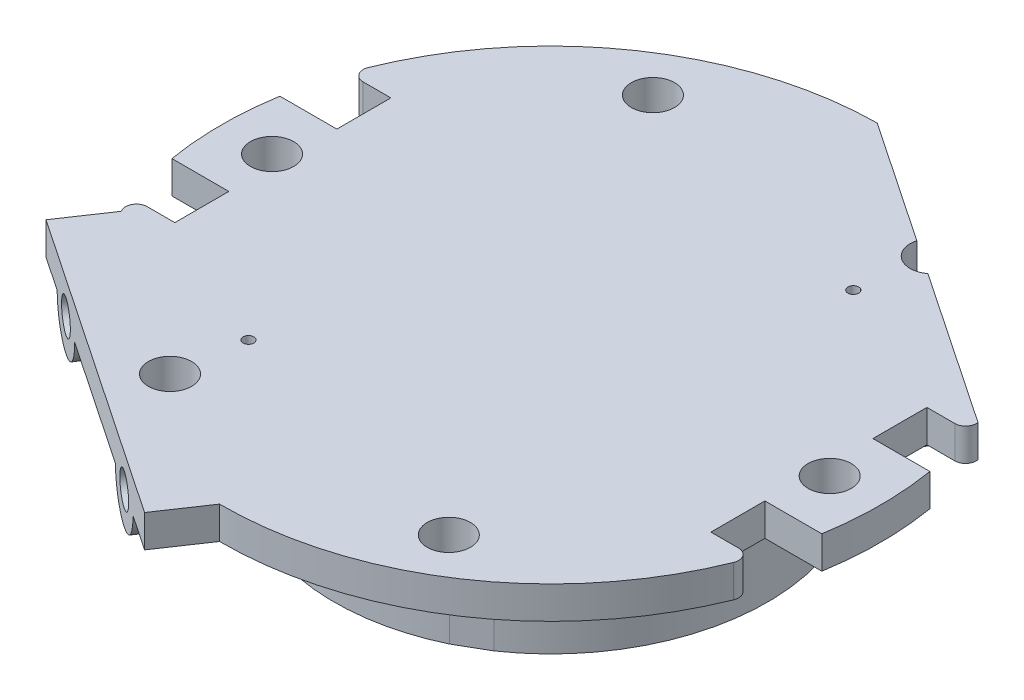
SolidWorks part; units mm, degrees
ref_plane "Alzado" through (0, 0, 0) normal (0, 0, 1) x (1, 0, 0)
ref_plane "Planta" through (0, 0, 0) normal (0, 1, 0) x (1, 0, 0)
ref_plane "Vista lateral" through (0, 0, 0) normal (1, 0, 0) x (0, 0, -1)
sketch "Croquis1" plane through (0, 0, 0) normal (0, 1, 0) x (1, 0, 0)
  circle A0 centre (0, 0) radius 30.5
extrude "Saliente-Extruir1" add sketch "Croquis1" along normal blind 3
sketch "Croquis5" plane through (0, 3, 0) normal (0, 1, 0) x (1, 0, 0)
  line L1 (28.8141, -5) -> (30.0874, -5)
  line L2 (28.8141, 5) -> (30.0874, 5)
  line L3 (-24.8141, 10) -> (-28.8141, 10)
  line L4 (24.8141, -5) -> (24.8141, -10)
  line L5 (-24.8141, -10) -> (-28.8141, -10)
  line L6 (24.8141, -5) -> (28.8141, -5)
  line L7 (24.8141, 5) -> (24.8141, 10)
  line L8 (-24.8141, 5) -> (-28.8141, 5)
  line L9 (-24.8141, 5) -> (-24.8141, 10)
  line L10 (-24.8141, -5) -> (-28.8141, -5)
  line L11 (-24.8141, -5) -> (-24.8141, -10)
  line L12 (24.8141, 5) -> (28.8141, 5)
  line L13 (24.8141, -10) -> (28.8141, -10)
  line L14 (24.8141, 10) -> (28.8141, 10)
  line L15 (-28.8141, 5) -> (-30.0874, 5)
  line L16 (-28.8141, -5) -> (-30.0874, -5)
  line L18 (-24.8141, 0) -> (-12.407, -21.4896)
  line L19 (-12.407, -21.4896) -> (12.407, -21.4896)
  line L20 (12.407, -21.4896) -> (24.8141, 0)
  line L21 (24.8141, 0) -> (12.407, 21.4896)
  line L22 (12.407, 21.4896) -> (-12.407, 21.4896)
  line L23 (-12.407, 21.4896) -> (-24.8141, 0)
  circle A0 centre (0, 0) radius 21.4896 construction
  circle A1 centre (0, 0) radius 30.5 construction
  arc A2 (-28.8141, 10) -> (-30.0874, 5) centre (0, 0) ccw
  arc A4 (-30.0874, -5) -> (-28.8141, -10) centre (0, 0) ccw
  arc A5 (30.0874, -5) -> (28.8141, -10) centre (0, 0) cw
  arc A6 (28.8141, 10) -> (30.0874, 5) centre (0, 0) cw
  circle M2 centre (0, 0) radius 30.5
extrude "Cortar-Extruir3" cut sketch "Croquis5" against normal blind 4 contours L10 L16 L5 L11 M2 | L15 L8 L9 L3 M2 | L14 L7 L12 L2 M2 | L4 L13 L1 L6 M2 region at (27.1844, 3, 7.3876) region at (-27.1844, 3, 7.3876) region at (27.1844, 3, -7.3876) region at (-27.1844, 3, -7.3876)
sketch "Croquis7" plane through (0, 3, 0) normal (0, 1, 0) x (1, 0, 0)
  line L2 (25.8141, 0) -> (12.907, 22.3556)
  line L3 (12.907, 22.3556) -> (-12.907, 22.3556)
  line L4 (-12.907, 22.3556) -> (-25.8141, 0)
  line L5 (-25.8141, 0) -> (-12.907, -22.3556)
  line L6 (-12.907, -22.3556) -> (12.907, -22.3556)
  line L7 (12.907, -22.3556) -> (25.8141, 0)
  circle A0 centre (25.8141, 0) radius 2
  circle A4 centre (-25.8141, 0) radius 2
  circle A5 centre (0, 0) radius 22.3556 construction
  circle A6 centre (12.907, 22.3556) radius 2
  circle A7 centre (-12.907, -22.3556) radius 2
  circle A8 centre (-12.907, 22.3556) radius 2
  circle A9 centre (12.907, -22.3556) radius 2
extrude "Cortar-Extruir4" cut sketch "Croquis7" against normal blind 10 contours A8 L4 L3 | A4 L4 L5 | A4 L5 L4 | A8 L3 L4 | L2 A6 L3 | L3 A6 L2 | L7 A0 L2 | L2 A0 L7 | A7 L5 L6 | A7 L6 L5 | L6 A9 L7 | L7 A9 L6 | A4 region at (24.7114, 3, 0) region at (26.3654, 3, 0) region at (12.3557, 3, -21.4007) region at (13.1827, 3, -22.8331) region at (13.1827, 3, 22.8331) region at (12.3557, 3, 21.4007) region at (-12.3557, 3, -21.4007) region at (-13.1827, 3, -22.8331) region at (-13.1827, 3, 22.8331) region at (-12.3557, 3, 21.4007) region at (-24.7114, 3, 0) region at (-26.3654, 3, 0)
sketch "Croquis8" plane through (0, 3, 0) normal (0, 1, 0) x (1, 0, 0)
  line L0 (0, 0) -> (12, 0)
  line L1 (12, 0) -> (12, 16)
  line L2 (0, 0) -> (-12, 0)
  line L3 (-12, 0) -> (-12, -16)
  circle A0 centre (12, 16) radius 0.5
  circle A1 centre (-12, -16) radius 0.5
extrude "Cortar-Extruir5" cut sketch "Croquis8" against normal blind 3 contours A1 | A0 region at (11.6564, 3, -16.3436) region at (-11.6564, 3, 15.6564)
sketch "Croquis9" plane through (0, 3, 0) normal (0, 1, 0) x (1, 0, 0)
  line L2 (-10, 17.3205) -> (-8.701, 18.0705)
  line L5 (25.6318, 16.5306) -> (27.1318, 13.9325)
  line L6 (-10, 17.3205) -> (-11.299, 16.5705)
  line L8 (10, -17.3205) -> (8.701, -18.0705)
  line L9 (10, -17.3205) -> (11.299, -16.5705)
  circle A0 centre (0, 0) radius 20.0562
  circle A1 centre (-12, -16) radius 3
  circle A2 centre (12, 16) radius 3
extrude "Saliente-Extruir2" add sketch "Croquis9" against normal blind 13 contours L2 L6 | L8 L9 region at (0, 3, 0)
sketch "Croquis11" plane through (14.0495, 0, -20.8293) normal (0.5592, 0, -0.829) x (-0.829, 0, -0.5592)
  line L1 (17.2916, 0) -> (-17.2916, 0)
  line L2 (17.2916, 0) -> (17.2916, 3)
  line L3 (17.2916, 3) -> (-17.2916, 3)
  line L4 (-17.2916, 0) -> (-17.2916, 3)
extrude "Saliente-Extruir3" add sketch "Croquis11" along normal blind 6
sketch "Croquis12" plane through (0, 3, 0) normal (0, 1, 0) x (1, 0, 0)
  circle A0 centre (12.907, 22.3556) radius 2
extrude "Cortar-Extruir7" cut sketch "Croquis12" against normal blind 3
sketch "Croquis13" plane through (17.4047, 0, -25.8035) normal (0.5592, 0, -0.829) x (-0.829, 0, -0.5592)
  line L0 (-17.2916, 0) -> (17.2916, 0)
  line L1 (17.2916, 3) -> (-17.2916, 3)
  line L2 (17.2916, 3) -> (-17.2916, 3) construction
  line L3 (17.2916, 0) -> (17.2916, 3) construction
  circle A1 centre (10, 0) radius 3
  circle A2 centre (-10, 0) radius 3
  circle A3 centre (10, 0) radius 1.5
  circle A5 centre (-10, 0) radius 1.5
  line M4 (-17.2916, 0) -> (17.2916, 0)
extrude "Saliente-Extruir4" add sketch "Croquis13" against normal blind 20 contours A3 L0 A1 | A3 L0 A1 | A5 L0 A2 | A5 L0 A2 | A5 M4 | A3 M4 region at (25.6951, 1.5671, -20.2116) region at (25.6951, -0.6366, -20.2116) region at (23.8297, -0.0671, -21.4698) region at (10.8337, 2.0739, -30.2358) region at (10.9797, -0.0671, -30.1373) region at (9.1143, -0.6366, -31.3955)
sketch "Croquis14" plane through (17.4047, 0, -25.8035) normal (0.5592, 0, -0.829) x (-0.829, 0, -0.5592)
  circle A0 centre (-10, 0) radius 1.5
  circle A1 centre (10, 0) radius 1.5
extrude "Cortar-Extruir8" cut sketch "Croquis14" against normal blind 6
sketch "Croquis15" plane through (0, 3, 0) normal (0, 1, 0) x (1, 0, 0)
  line L0 (28.3849, 11.16) -> (-0.2859, 30.4987)
  line L1 (28.3849, 11.16) -> (0.1409, -30.7136)
  line L2 (-0.2859, 30.4987) -> (-28.5299, -11.3749)
  line L3 (0.1409, -30.7136) -> (-28.5299, -11.3749)
  circle A0 centre (-0.2859, 0) radius 30.7165
  arc M12 (-28.8141, -10) -> (28.8141, -10) centre (0, 0) ccw
  circle M28 centre (-12.907, -22.3556) radius 2
extrude "Cortar-Extruir9" cut sketch "Croquis15" against normal blind 3 contours L3 M12 M28 region at (-15.494, 3, 22.7434)
sketch "Croquis16" plane through (-14.1945, 0, 21.0442) normal (-0.5592, 0, 0.829) x (0.829, 0, 0.5592)
  line L0 (-16.9088, 0) -> (-16.9088, 3)
  line L1 (-16.9088, 0) -> (16.78, 0)
  line L2 (-16.9088, 3) -> (16.78, 3)
  line L3 (16.78, 0) -> (16.78, 3)
extrude "Saliente-Extruir5" add sketch "Croquis16" along normal blind 6
sketch "Croquis17" plane through (0, 3, 0) normal (0, 1, 0) x (1, 0, 0)
  circle A0 centre (-12.907, -22.3556) radius 2
extrude "Cortar-Extruir10" cut sketch "Croquis17" against normal blind 3
sketch "Croquis18" plane through (-17.5497, 0, 26.0185) normal (-0.5592, 0, 0.829) x (0.829, 0, 0.5592)
  line L2 (-16.9088, 0) -> (16.78, 0) construction
  circle A0 centre (9.9356, 0) radius 3
  circle A1 centre (-10.0644, 0) radius 3
extrude "Saliente-Extruir6" add sketch "Croquis18" against normal blind 25
sketch "Croquis19" plane through (-17.5497, 0, 26.0185) normal (-0.5592, 0, 0.829) x (0.829, 0, 0.5592)
  circle A0 centre (-10.0644, 0) radius 1.5
  circle A1 centre (9.9356, 0) radius 1.5
extrude "Cortar-Extruir11" cut sketch "Croquis19" against normal blind 5
sketch "Croquis20" plane through (17.4047, 0, -25.8035) normal (0.5592, 0, -0.829) x (-0.829, 0, -0.5592)
  line L0 (17.2916, 3) -> (17.2916, 0)
  line L1 (17.2916, 0) -> (13, 0)
  line L2 (-7, 0) -> (7, 0) construction
  line L3 (7, 0) -> (-7, 0)
  line L4 (-13, 0) -> (-17.2916, 0)
  line L5 (-17.2916, 0) -> (-17.2916, 3)
  line L6 (-17.2916, 3) -> (17.2916, 3)
  arc A0 (13, 0) -> (7, 0) centre (10, 0) cw
  arc A1 (7, 0) -> (13, 0) centre (10, 0) ccw construction
  arc A2 (-7, 0) -> (-13, 0) centre (-10, 0) cw
extrude "Cortar-Extruir12" cut sketch "Croquis20" against normal blind 6
sketch "Croquis21" plane through (-17.5497, 0, 26.0185) normal (-0.5592, 0, 0.829) x (0.829, 0, 0.5592)
  line L0 (-13.0644, 0) -> (-16.9088, 0)
  line L1 (-16.9088, 0) -> (-16.9088, 3)
  line L2 (-16.9088, 3) -> (16.78, 3)
  line L3 (16.78, 3) -> (16.78, 0)
  line L4 (16.78, 0) -> (12.9356, 0)
  line L5 (6.9356, 0) -> (-7.0644, 0)
  arc A0 (-13.0644, 0) -> (-7.0644, 0) centre (-10.0644, 0) ccw
  arc A1 (6.9356, 0) -> (12.9356, 0) centre (9.9356, 0) ccw
extrude "Cortar-Extruir13" cut sketch "Croquis21" against normal blind 6
sketch "Croquis22" plane through (-14.1945, 0, 21.0442) normal (-0.5592, 0, 0.829) x (0.829, 0, 0.5592)
  circle A0 centre (-10.0644, 0) radius 1.5
  circle A1 centre (9.9356, 0) radius 1.5
extrude "Cortar-Extruir14" cut sketch "Croquis22" against normal blind 6
sketch "Croquis23" plane through (14.0495, 0, -20.8293) normal (0.5592, 0, -0.829) x (-0.829, 0, -0.5592)
  circle A0 centre (-10, 0) radius 1.5
  circle A1 centre (10, 0) radius 1.5
extrude "Cortar-Extruir15" cut sketch "Croquis23" against normal blind 6
fillet "Redondeo1" radius 1 4 edges at (-28.8141, 1.5, -10) (-28.8141, 1.5, 10) (28.8141, 1.5, 10) (28.8141, 1.5, -10)
sketch "Croquis24" plane through (-14.1945, 0, 21.0442) normal (-0.5592, 0, 0.829) x (0.829, 0, 0.5592)
  line L0 (16.9088, 3) -> (16.9088, 0)
  line L1 (16.9088, 0) -> (12.9356, 0)
  line L2 (6.9356, 0) -> (-7.0644, 0)
  line L3 (-13.0644, 0) -> (-16.9088, 0)
  line L4 (-16.9088, 0) -> (-16.9088, 3)
  line L5 (-16.9088, 3) -> (16.9088, 3)
  arc A0 (6.9356, 0) -> (12.9356, 0) centre (9.9356, 0) ccw
  arc A1 (-13.0644, 0) -> (-7.0644, 0) centre (-10.0644, 0) ccw
  circle A2 centre (-10.0644, 0) radius 1.5
  circle A3 centre (9.9356, 0) radius 1.5
extrude "Saliente-Extruir7" add sketch "Croquis24" along normal blind 5
sketch "Croquis25" plane through (0, 3, 0) normal (0, 1, 0) x (1, 0, 0)
  circle A0 centre (-12.907, -22.3556) radius 2
extrude "Cortar-Extruir16" cut sketch "Croquis25" against normal blind 3
